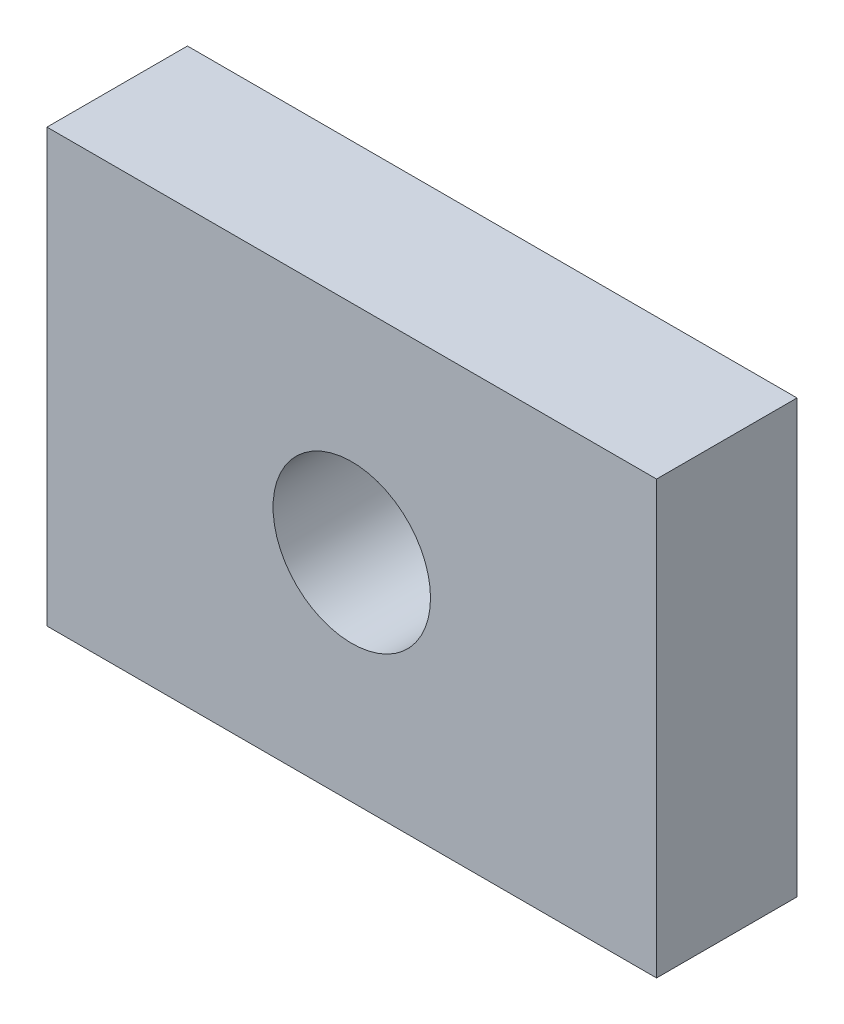
SolidWorks part; units mm, degrees
ref_plane "Front Plane" through (0, 0, 0) normal (0, 0, 1) x (1, 0, 0)
ref_plane "Top Plane" through (0, 0, 0) normal (0, 1, 0) x (1, 0, 0)
ref_plane "Right Plane" through (0, 0, 0) normal (1, 0, 0) x (0, 0, -1)
sketch "Sketch1" plane through (0, 0, 0) normal (0, 0, 1) x (1, 0, 0)
  line L1 (-55.1185, -39.0725) -> (55.1185, -39.0725)
  line L2 (-55.1185, -39.0725) -> (-55.1185, 39.0725)
  line L3 (-55.1185, 39.0725) -> (55.1185, 39.0725)
  line L4 (55.1185, -39.0725) -> (55.1185, 39.0725)
  line L5 (-55.1185, -39.0725) -> (55.1185, 39.0725) construction
  line L6 (-55.1185, 39.0725) -> (55.1185, -39.0725) construction
  point P0 (0, 0)
extrude "Boss-Extrude1" add sketch "Sketch1" against normal blind 25.4
sketch "Sketch2" plane through (0, 0, 0) normal (0, 0, 1) x (1, 0, 0)
  circle A0 centre (0, 0) radius 14.2365
extrude "Cut-Extrude1" cut sketch "Sketch2" against normal through all
